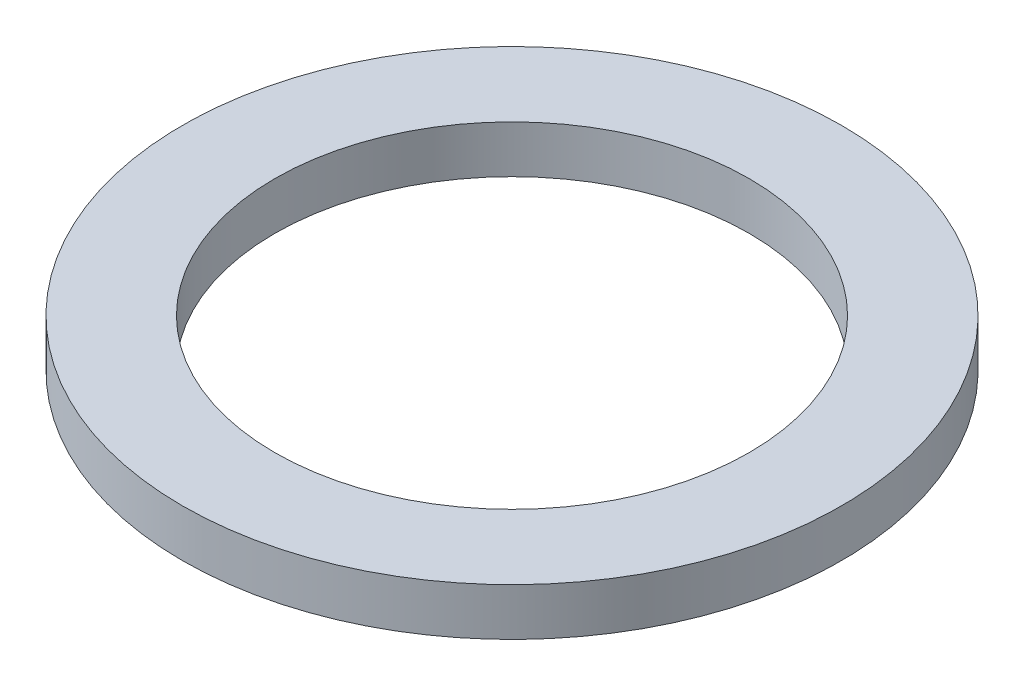
SolidWorks part; units mm, degrees
ref_plane "Front Plane" through (0, 0, 0) normal (0, 0, 1) x (1, 0, 0)
ref_plane "Top Plane" through (0, 0, 0) normal (0, 1, 0) x (1, 0, 0)
ref_plane "Right Plane" through (0, 0, 0) normal (1, 0, 0) x (0, 0, -1)
sketch "Sketch1" plane through (0, 0, 0) normal (0, 1, 0) x (1, 0, 0)
  circle A0 centre (0, 0) radius 62.5
  dimension "FLANGE_OD" = 125
extrude "Boss-Extrude1" add sketch "Sketch1" along normal blind 9
sketch "Sketch2" plane through (0, 0, 0) normal (0, 1, 0) x (1, 0, 0)
  circle A0 centre (0, 0) radius 45
  dimension "BORE_D" = 90
extrude "Cut-Extrude1" cut sketch "Sketch2" along normal through all
sketch "Sketch3" plane through (0, 9, 0) normal (0, 1, 0) x (1, 0, 0)
  circle A0 centre (0, 0) radius 28.1372 construction
  circle A1 centre (-28.1372, 0) radius 1.7211
  dimension "BOLT_D" = 3.4422
  dimension "BOLT_PCD" = 56.2745
extrude "Cut-Extrude2" cut sketch "Sketch3" against normal blind 6.8562 rebuild error yes
pattern_circular "CirPattern1" count 5 over 360 rebuild error yes
